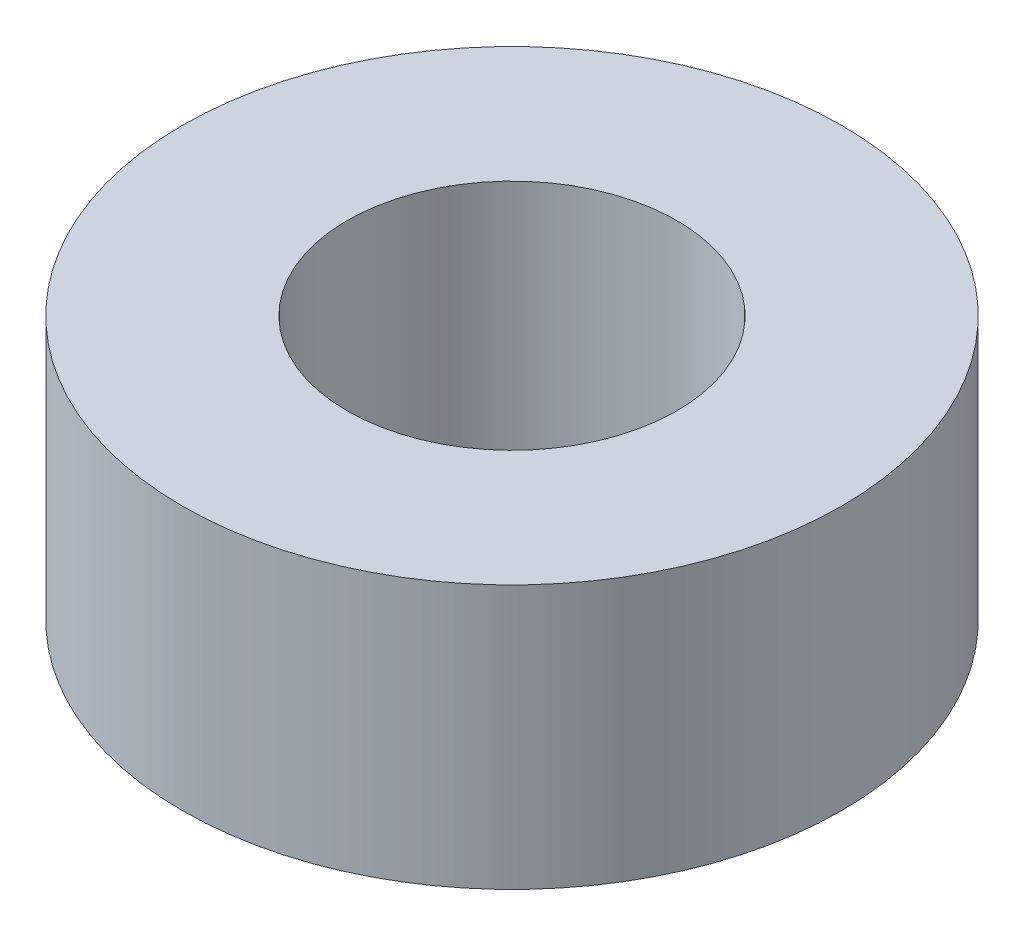
SolidWorks part; units mm, degrees
ref_plane "Front Plane" through (0, 0, 0) normal (0, 0, 1) x (1, 0, 0)
ref_plane "Top Plane" through (0, 0, 0) normal (0, 1, 0) x (1, 0, 0)
ref_plane "Right Plane" through (0, 0, 0) normal (1, 0, 0) x (0, 0, -1)
sketch "Sketch1" plane through (0, 0, 0) normal (0, 1, 0) x (1, 0, 0)
  circle A0 centre (0, 0) radius 30
  dimension "FLANGE_OD" = 60
extrude "Boss-Extrude1" add sketch "Sketch1" along normal blind 24
sketch "Sketch2" plane through (0, 0, 0) normal (0, 1, 0) x (1, 0, 0)
  circle A0 centre (0, 0) radius 15
  dimension "BORE_D" = 30
extrude "Cut-Extrude1" cut sketch "Sketch2" along normal through all
sketch "Sketch3" plane through (0, 24, 0) normal (0, 1, 0) x (1, 0, 0)
  circle A0 centre (0, 0) radius 12.5172 construction
  circle A1 centre (-12.5172, 0) radius 1.8404
  dimension "BOLT_D" = 3.6808
  dimension "BOLT_PCD" = 25.0344
extrude "Cut-Extrude2" cut sketch "Sketch3" against normal blind 14.9124 rebuild error yes
pattern_circular "CirPattern1" count 8 over 360 rebuild error yes
